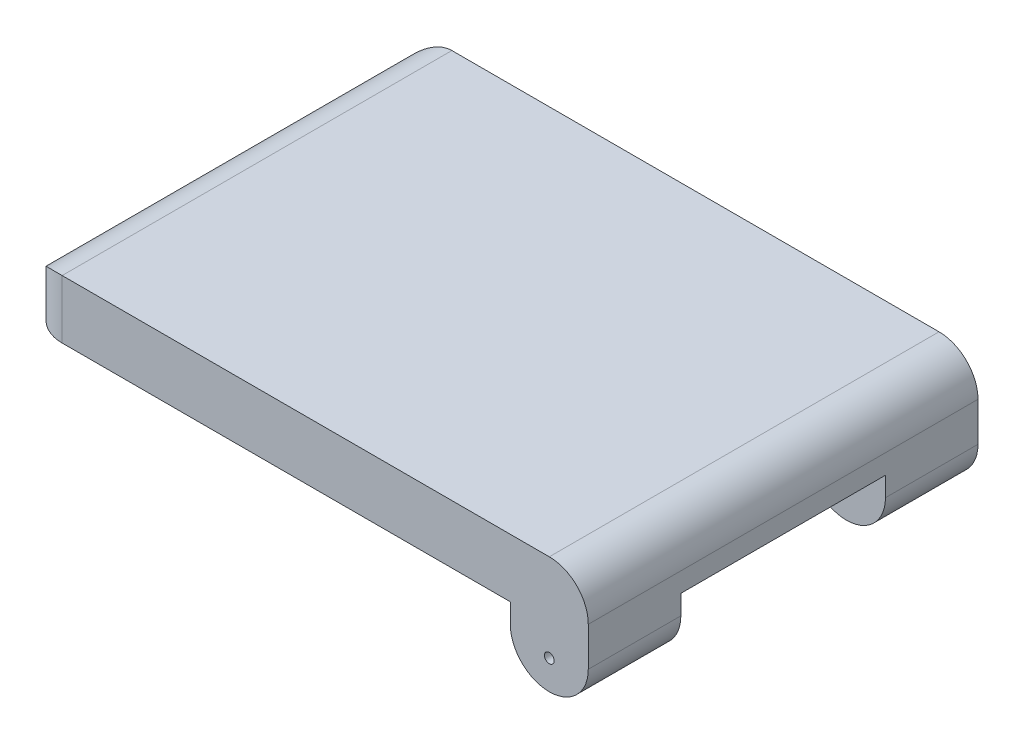
SolidWorks part; units mm, degrees
material "Hexcel AS4C (3000 волосков)"
ref_plane "Спереди" through (0, 0, 0) normal (0, 0, 1) x (1, 0, 0)
ref_plane "Сверху" through (0, 0, 0) normal (0, 1, 0) x (1, 0, 0)
ref_plane "Справа" through (0, 0, 0) normal (1, 0, 0) x (0, 0, -1)
sketch "Эскиз5" plane through (0, 0, 0) normal (0, 1, 0) x (1, 0, 0)
  line L0 (-71.6731, 130.4652) -> (-129.6731, 130.4652) construction
  line L1 (-129.6731, 110.4652) -> (-71.6731, 110.4652)
  line L2 (-129.6731, 110.4652) -> (-129.6731, 150.4652)
  line L3 (-129.6731, 150.4652) -> (-71.6731, 150.4652)
  line L4 (-71.6731, 110.4652) -> (-71.6731, 150.4652)
  line L5 (-71.6731, 130.4652) -> (-71.6731, 119.9652) construction
  line L6 (-71.6731, 119.9652) -> (-79.6731, 119.9652) construction
  line L7 (-79.6731, 119.9652) -> (-79.6731, 110.4652) construction
  line L8 (-79.6731, 110.4652) -> (-129.6731, 110.4652) construction
  line L9 (-71.6731, 130.4652) -> (-71.6731, 140.9652) construction
  line L10 (-71.6731, 140.9652) -> (-79.6731, 140.9652) construction
  line L11 (-79.6731, 140.9652) -> (-79.6731, 150.4652) construction
  line L12 (-79.6731, 150.4652) -> (-129.6731, 150.4652) construction
  dimension "D1" = 58
  dimension "D2" = 40
extrude "Бобышка-Вытянуть3" add sketch "Эскиз5" along normal blind 6
sketch "Эскиз6" plane through (0, 0, 0) normal (0, -1, 0) x (1, 0, 0)
  line L1 (-71.6731, -110.4652) -> (-79.6731, -110.4652)
  line L2 (-71.6731, -110.4652) -> (-71.6731, -119.9652)
  line L3 (-71.6731, -119.9652) -> (-79.6731, -119.9652)
  line L4 (-79.6731, -110.4652) -> (-79.6731, -119.9652)
  line L5 (-71.6731, -150.4652) -> (-79.6731, -150.4652)
  line L6 (-71.6731, -150.4652) -> (-71.6731, -140.9652)
  line L7 (-71.6731, -140.9652) -> (-79.6731, -140.9652)
  line L8 (-79.6731, -150.4652) -> (-79.6731, -140.9652)
extrude "Бобышка-Вытянуть4" add sketch "Эскиз6" along normal blind 6
sketch "Эскиз7" plane through (0, 0, -110.4652) normal (0, 0, 1) x (1, 0, 0)
  line L0 (-79.6731, -3) -> (-71.6731, -3) construction
  line L1 (-79.6731, -6) -> (-79.6731, 0) construction
  line L2 (-71.6731, 6) -> (-71.6731, -6) construction
  line L3 (-75.6731, -6) -> (-75.6731, 6) construction
  line L4 (-71.6731, -6) -> (-79.6731, -6) construction
  line L5 (-129.6731, 6) -> (-71.6731, 6) construction
  circle A0 centre (-75.6731, -3) radius 0.5
extrude "Вырез-Вытянуть2" cut sketch "Эскиз7" against normal up to surface (40 mm away) up to face at (-93.6731, 0, -150.4652)
fillet "Скругление4" radius 4 5 edges at (-71.6731, 6, -130.4652) (-71.6731, -6, -145.7152) (-79.6731, -6, -145.7152) (-71.6731, -6, -115.2152) (-79.6731, -6, -115.2152)
fillet "Скругление5" radius 4 3 edges at (-129.6731, 6, -130.4652) (-129.6731, 3, -110.4652) (-129.6731, 3, -150.4652)
